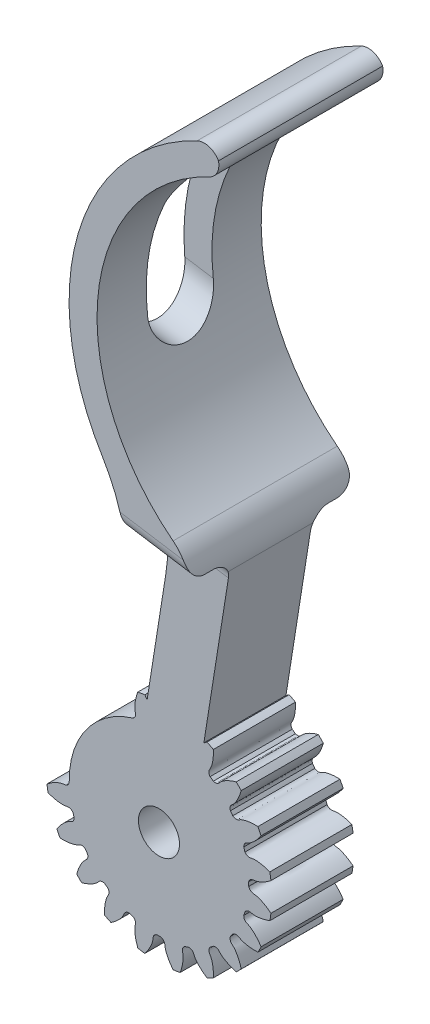
SolidWorks part; units mm, degrees
material "聚脂树脂"
ref_plane "前视基准面" through (0, 0, 0) normal (0, 0, 1) x (1, 0, 0)
ref_plane "上视基准面" through (0, 0, 0) normal (0, 1, 0) x (1, 0, 0)
ref_plane "右视基准面" through (0, 0, 0) normal (1, 0, 0) x (0, 0, -1)
other "Configuration Table"
sketch "草图1" plane through (0, 0, 0) normal (0, 0, 1) x (1, 0, 0)
  circle A0 centre (0, 0) radius 13.75
extrude "凸台-拉伸1" add sketch "草图1" along normal blind 10
ref_axis "基准轴1" through (0, 0, -1.5) along (0, 0, 1)
sketch "草图2" plane through (0, 0, 0) normal (0, 0, 1) x (1, 0, 0)
  line L0 (0, 0) -> (0, 13.75) construction
  circle A0 centre (0, 0) radius 13.75 construction
  arc A1 (0.2416, 10.9348) -> (-0.2416, 10.9348) centre (0, 0) ccw
  arc A2 (3.9764, 15.6228) -> (-3.9764, 15.6228) centre (0, 0) ccw
  spline S0 degree 3 poles (0.2416, 10.9348) (0.764, 11.1168) (0.6964, 11.4839) (0.7661, 11.8375) (0.7736, 11.8719) (0.7829, 11.9108) (0.7941, 11.954) (0.8075, 12.0015) (0.8231, 12.0532) (0.8413, 12.1091) (0.8621, 12.169) (0.8857, 12.2329) (0.9123, 12.3007) (0.9421, 12.3723) (0.9752, 12.4476) (1.0117, 12.5264) (1.0519, 12.6088) (1.0959, 12.6945) (1.1438, 12.7834) (1.1957, 12.8755) (1.2519, 12.9705) (1.3125, 13.0684) (1.3775, 13.1691) (1.4472, 13.2723) (1.5216, 13.3779) (1.601, 13.4858) (1.6853, 13.5958) (1.7747, 13.7078) (1.8694, 13.8216) (1.9693, 13.937) (2.0748, 14.0539) (2.1857, 14.1721) (2.3023, 14.2914) (2.4246, 14.4116) (2.5527, 14.5326) (2.6866, 14.6542) (2.8265, 14.7761) (2.9725, 14.8983) (3.1245, 15.0204) (3.2826, 15.1424) (3.4469, 15.2639) (3.6768, 15.427) (3.8549, 15.5454) (3.9764, 15.6228) knots 0 0 0 0 0.165916 0.170906 0.176664 0.183189 0.190482 0.198542 0.207371 0.216967 0.22733 0.238462 0.250361 0.263027 0.276462 0.290664 0.305634 0.321371 0.337876 0.355149 0.37319 0.391998 0.411574 0.431917 0.453028 0.474907 0.497554 0.520968 0.54515 0.570099 0.595817 0.622302 0.649554 0.677575 0.706363 0.735918 0.766242 0.797333 0.829191 0.861818 0.895212 0.929373 1 1 1 1
  spline S1 degree 3 poles (-0.2416, 10.9348) (-0.764, 11.1168) (-0.6964, 11.4839) (-0.7661, 11.8375) (-0.7736, 11.8719) (-0.7829, 11.9108) (-0.7941, 11.954) (-0.8075, 12.0015) (-0.8231, 12.0532) (-0.8413, 12.1091) (-0.8621, 12.169) (-0.8857, 12.2329) (-0.9123, 12.3007) (-0.9421, 12.3723) (-0.9752, 12.4476) (-1.0117, 12.5264) (-1.0519, 12.6088) (-1.0959, 12.6945) (-1.1438, 12.7834) (-1.1957, 12.8755) (-1.2519, 12.9705) (-1.3125, 13.0684) (-1.3775, 13.1691) (-1.4472, 13.2723) (-1.5216, 13.3779) (-1.601, 13.4858) (-1.6853, 13.5958) (-1.7747, 13.7078) (-1.8694, 13.8216) (-1.9693, 13.937) (-2.0748, 14.0539) (-2.1857, 14.1721) (-2.3023, 14.2914) (-2.4246, 14.4116) (-2.5527, 14.5326) (-2.6866, 14.6542) (-2.8265, 14.7761) (-2.9725, 14.8983) (-3.1245, 15.0204) (-3.2826, 15.1424) (-3.4469, 15.2639) (-3.6768, 15.427) (-3.8549, 15.5454) (-3.9764, 15.6228) knots 0 0 0 0 0.165916 0.170906 0.176664 0.183189 0.190482 0.198542 0.207371 0.216967 0.22733 0.238462 0.250361 0.263027 0.276462 0.290664 0.305634 0.321371 0.337876 0.355149 0.37319 0.391998 0.411574 0.431917 0.453028 0.474907 0.497554 0.520968 0.54515 0.570099 0.595817 0.622302 0.649554 0.677575 0.706363 0.735918 0.766242 0.797333 0.829191 0.861818 0.895212 0.929373 1 1 1 1
extrude "切除-拉伸1" cut sketch "草图2" along normal through all
pattern_circular "阵列(圆周)1" count 20 every 18 about axis through (0, 0, -1.5) along (0, 0, 1) of "切除-拉伸1"
sketch "草图3" plane through (0, 0, 0) normal (0, 0, 1) x (1, 0, 0)
  circle A0 centre (0, 0) radius 12.5 construction
  dimension "Dn" = 25
sketch "草图6" plane through (0, 0, 0) normal (0, 0, -1) x (-1, 0, 0)
  line L0 (0, 0) -> (-10.311, 65.1009) construction
  line L1 (0, 0) -> (38.9643, 6.1713) construction
  line L2 (0, 0) -> (-30.4582, -4.8241) construction
  line L3 (-12.3461, -1.9554) -> (-21.1812, 53.827) construction
  line L4 (3.4569, 0.5475) -> (-2.1703, 36.0761)
  line L5 (-3.4569, -0.5475) -> (-9.0841, 34.981)
  line L6 (-9.0841, 34.981) -> (-15.0031, 72.3522)
  line L7 (-15.0031, 72.3522) -> (-21.4537, 55.5478) construction
  line L8 (-15.0031, 72.3522) -> (-7.9754, 90.6601) construction
  line L9 (-15.0031, 72.3522) -> (-11.6329, 81.132)
  line L10 (-3.4569, -0.5475) -> (3.4569, 0.5475)
  circle A0 centre (0, 0) radius 12.5 construction
  circle A1 centre (-21.4537, 55.5478) radius 24 construction
  circle A2 centre (-21.4537, 55.5478) radius 27.4044 construction
  arc A3 (-11.6329, 81.132) -> (-2.1703, 36.0761) centre (-21.4537, 55.5478) cw
  arc A4 (-12.8529, 77.9537) -> (-9.0841, 34.981) centre (-21.4537, 55.5478) cw
  dimension "D1" = 25
  dimension "D4" = 48
  dimension "D5" = 30
  dimension "D2" = 7
  dimension "D3" = 58.22
extrude "凸台-拉伸2" add sketch "草图6" against normal blind 15 and the other way blind 5 contours A3 L9 L6 L5 L10 L4 | L5 | L4 region at (0.1311, 0.8278, 0)
sketch "草图7" plane through (-3.4569, 0.5475, 0) normal (0.9877, -0.1564, 0) x (0, 0, -1)
  line L0 (0, 0) -> (0, 34)
  line L1 (0, 34) -> (5, 34)
  line L3 (5, 34) -> (5, 0)
  line L4 (5, 0) -> (0, 0) construction
  line L5 (5, 0) -> (5, 35.9714) construction
  line L6 (5, 0) -> (0, 0)
  line L7 (-5, 4.6588) -> (-5, 27.3083) construction
  line L8 (-10, 4.6588) -> (0, 4.6588) construction
  line L9 (-15, 34) -> (-15, 0)
  line L10 (-10, 34) -> (-15, 34)
  line L11 (-10, 0) -> (-10, 34)
  line L12 (-15, 0) -> (-10, 0)
  dimension "D1" = 34
extrude "切除-拉伸3" cut sketch "草图7" against normal blind 32 and the other way blind 10
ref_plane "基准面1" through (12.5, 0, 0) normal (1, 0, 0) x (0, 0, -1)
ref_axis "基准轴2" through (0, 0, -6) along (0, 0, 1)
ref_plane "基准面2" through (0, 0, 0) normal (-0.9877, 0.1564, 0) x (0, 0, 1)
ref_plane "基准面3" through (12.3461, -1.9554, 0) normal (-0.9877, 0.1564, 0) x (0, 0, 1)
sketch "草图13" plane through (12.3461, -1.9554, 0) normal (-0.9877, 0.1564, 0) x (0, 0, 1)
  line L0 (5, 0.4331) -> (5, 90.5431) construction
  line L1 (0, 0.4331) -> (10, 0.4331) construction
  line L2 (5, 82.6531) -> (5, 34.6531)
  arc A0 (5, 82.6531) -> (5, 34.6531) centre (5, 58.6531) cw
  dimension "D1" = 24
  dimension "D2" = 58.22
sketch "草图12" plane through (0, 0, -5) normal (0, 0, -1) x (-1, 0, 0)
  line L0 (0, 0) -> (-14.3434, 90.5607) construction
  line L1 (-12.3461, -1.9554) -> (-26.4984, 87.3984) construction
  line L2 (-11.6703, 81.0345) -> (-11.6329, 81.132)
  line L3 (0, 0) -> (-28.4747, -4.5099) construction
  line L4 (-2.1703, 36.0761) -> (-2.1904, 36.2032)
  line L5 (-1.8619, 34.1289) -> (-2.1703, 36.0761) construction
  line L6 (-12.8529, 77.9537) -> (-11.6329, 81.132) construction
  circle A0 centre (-21.4537, 55.5478) radius 28.3019
  circle A1 centre (-21.4537, 55.5478) radius 27.3
  dimension "D3" = 54.6
  dimension "D4" = 56.6039
  dimension "D1" = 12.5
  dimension "D2" = 58.22
fillet "圆角2" radius 2 4 edges at (5.3188, 33.5814, 10) (5.3188, 33.5814, 15) (5.3188, 33.5814, 0) (5.3188, 33.5814, -5)
sketch "草图16" plane through (0, 0, 10) normal (0, 0, 1) x (1, 0, 0)
  circle A0 centre (0, 0) radius 2.5
  dimension "D1" = 5
extrude "切除-拉伸5" cut sketch "草图16" against normal blind 16.5
sketch "草图19" plane through (0, 0, 0) normal (0, 0, -1) x (-1, 0, 0)
  circle A0 centre (0, 0) radius 8
  dimension "D1" = 16
extrude "切除-拉伸7" cut sketch "草图19" against normal blind 3.4
sketch "草图20" plane through (0, 0, 0) normal (0, 0, -1) x (-1, 0, 0)
  line L0 (0, 0) -> (3.6089, 10.325)
  line L1 (3.6089, 10.325) -> (7.1451, 20.4421)
  line L2 (0, 0) -> (10.9348, -0.2416)
  line L3 (10.9348, -0.2416) -> (20.7519, -0.2416)
  circle A0 centre (0, 0) radius 17.5
  circle A1 centre (0, 0) radius 10.9375
  arc A2 (-8.7044, 6.6228) -> (-8.9885, 6.2318) centre (0, 0) ccw construction
  dimension "D1" = 35
extrude "切除-拉伸8" cut sketch "草图20" against normal blind 10 contours A1 L3 A0 L1 region at (-11.1082, 7.7459, 0)
sketch "草图21" plane through (12.3461, -1.9554, 0) normal (-0.9877, 0.1564, 0) x (0, 0, 1)
  line L0 (5, -3.835) -> (5, 83.7015) construction
  line L1 (0, -3.835) -> (10, -3.835) construction
  circle A0 centre (5, 58.22) radius 4
  dimension "D1" = 8
  dimension "D2" = 58.22
fillet "圆角3" radius 20 1 edges at (2.1703, 36.0761, 5)
fillet "圆角4" radius 5 1 edges at (9.0841, 34.981, 5)
fillet "圆角5" radius 2 2 edges at (12.8529, 77.9537, 5) (11.6329, 81.132, 5)
sketch "草图22" plane through (12.3461, -1.9554, 0) normal (-0.9877, 0.1564, 0) x (0, 0, 1)
  line L0 (5, -1.9493) -> (5, 109.7629) construction
  line L1 (10, -1.9493) -> (0, -1.9493) construction
  line L2 (5, 64.72) -> (5, 51.72) construction
  line L3 (9, 64.72) -> (9, 51.72)
  line L4 (1, 64.72) -> (1, 51.72)
  arc A0 (9, 64.72) -> (1, 64.72) centre (5, 64.72) ccw
  arc A1 (1, 51.72) -> (9, 51.72) centre (5, 51.72) ccw
  point P6 (5, 58.22)
  dimension "D1" = 4
  dimension "D2" = 13
  dimension "D3" = 58.22
extrude "切除-拉伸9" cut sketch "草图22" along normal blind 45
